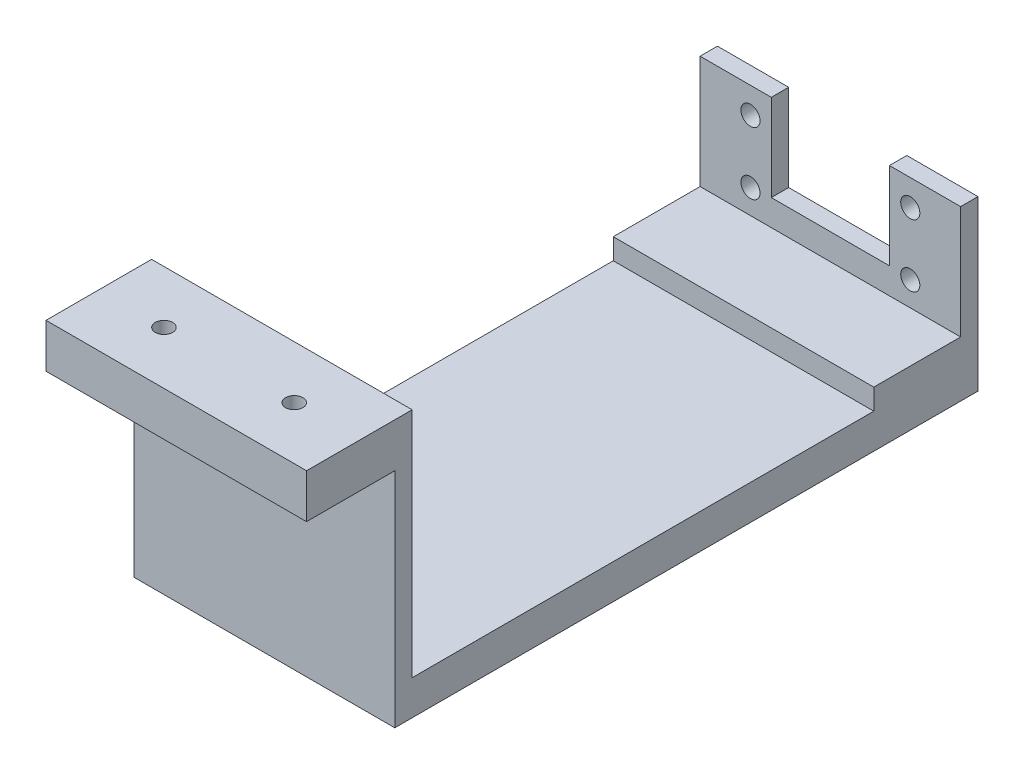
SolidWorks part; units mm, degrees
material "ABS"
ref_plane "Front Plane" through (0, 0, 0) normal (0, 0, 1) x (1, 0, 0)
ref_plane "Top Plane" through (0, 0, 0) normal (0, 1, 0) x (1, 0, 0)
ref_plane "Right Plane" through (0, 0, 0) normal (1, 0, 0) x (0, 0, -1)
sketch "Sketch1" plane through (0, 0, 0) normal (0, 0, 1) x (1, 0, 0)
  line L0 (20.5, 32.5) -> (20.5, 7.5)
  line L1 (0, 0) -> (75, 0)
  line L2 (0, 0) -> (0, 32.5)
  line L3 (0, 32.5) -> (75, 32.5)
  line L4 (75, 0) -> (75, 32.5)
  line L5 (20.5, 7.5) -> (54.5, 7.5)
  line L6 (54.5, 7.5) -> (54.5, 32.5)
  line L7 (37.5, 32.5) -> (37.5, 0) construction
  circle A0 centre (14.5, 25) radius 2.75
  circle A1 centre (14.5, 7) radius 2.75
  circle A2 centre (60.5, 7) radius 2.75
  circle A3 centre (60.5, 25) radius 2.75
  dimension "D6" = 5.5
  dimension "D7" = 46
  dimension "D8" = 34
  dimension "D1" = 32.5
  dimension "D2" = 75
  dimension "D3" = 17
  dimension "D4" = 18
  dimension "D5" = 25
  dimension "D9" = 25
extrude "Boss-Extrude1" add sketch "Sketch1" along normal blind 5 contours L7 L5 L0 L3 L2 L1 A1 A0 | L5 L7 L1 L4 L3 L6 A3 A2 region at (13.183, 14.1302, 0) region at (61.817, 14.1302, 0)
sketch "Sketch2" plane through (0, 0, 5) normal (0, 0, 1) x (1, 0, 0)
  line L0 (75, 0) -> (75, 32.5) construction
  line L1 (0, 0) -> (75, 0)
  line L2 (0, 0) -> (0, -6)
  line L3 (0, -6) -> (75, -6)
  line L4 (75, 0) -> (75, -6)
  dimension "D1" = 6
extrude "Boss-Extrude2" add sketch "Sketch2" along normal blind 25 and the other way blind 5
sketch "Sketch3" plane through (0, 0, 0) normal (0, 0, -1) x (-1, 0, 0)
  line L0 (0, -6) -> (0, 32.5) construction
  line L1 (-75, -6) -> (0, -6)
  line L2 (-75, -6) -> (-75, -16)
  line L3 (-75, -16) -> (0, -16)
  line L4 (0, -6) -> (0, -16)
  dimension "D1" = 10
extrude "Boss-Extrude3" add sketch "Sketch3" against normal blind 167.8942
sketch "Sketch4" plane through (0, -6, 0) normal (0, 1, 0) x (1, 0, 0)
  line L0 (75, -167.8942) -> (75, -30) construction
  line L1 (0, -167.8942) -> (75, -167.8942)
  line L2 (0, -167.8942) -> (0, -162.8942)
  line L3 (0, -162.8942) -> (75, -162.8942)
  line L4 (75, -167.8942) -> (75, -162.8942)
  dimension "D1" = 5
extrude "Boss-Extrude4" add sketch "Sketch4" along normal blind 66.8
sketch "Sketch5" plane through (0, 0, 167.8942) normal (0, 0, 1) x (1, 0, 0)
  line L0 (0, -16) -> (0, 60.8) construction
  line L1 (0, 48.1) -> (75, 48.1)
  line L2 (0, 48.1) -> (0, 60.8)
  line L3 (0, 60.8) -> (75, 60.8)
  line L4 (75, 48.1) -> (75, 60.8)
  line L5 (75, 60.8) -> (75, -16) construction
  line L6 (0, 60.8) -> (75, 60.8) construction
  dimension "D2" = 12.7
extrude "Boss-Extrude5" add sketch "Sketch5" along normal blind 25.4
sketch "Sketch6" plane through (0, 60.8, 0) normal (0, 1, 0) x (1, 0, 0)
  line L0 (0, -178.0942) -> (37.5, -178.0942) construction
  line L1 (37.5, -193.2942) -> (37.5, -162.8942) construction
  line L2 (75, -178.0942) -> (37.5, -178.0942) construction
  line L5 (0, -162.8942) -> (0, -193.2942)
  line L6 (0, -193.2942) -> (75, -193.2942)
  line L7 (75, -193.2942) -> (75, -162.8942)
  line L9 (0, -162.8942) -> (0, -193.2942)
  line L10 (0, -193.2942) -> (75, -193.2942)
  line L11 (75, -193.2942) -> (75, -162.8942)
  line L40 (75, -162.8942) -> (0, -162.8942)
  line L41 (75, -162.8942) -> (0, -162.8942)
  point P4 (18.75, -178.0942)
  point P10 (56.25, -178.0942)
  point P75 (0, 0)
  dimension "D1" = 0
hole_wizard "M5x0.8 Tapped Hole1" positions "Sketch6" profile "Sketch7" tap size "M5x0.8" standard "ANSI Metric" end condition through all
sketch "Sketch7" plane through (56.25, 60.8, 178.0942) normal (1, 0, 0) x (0, 0, 1)
  line L0 (0, 0) -> (0, 76.8)
  line L1 (0, 76.8) -> (2.5, 76.8)
  line L2 (2.5, 76.8) -> (2.5, 0)
  line L5 (2.5, 0) -> (0, 0)
  line L11 (0, -6.35) -> (0, 107.95) construction
  dimension "Thread Major Dia." = 5
  dimension "Thru Tap Drill Depth" = 76.8
